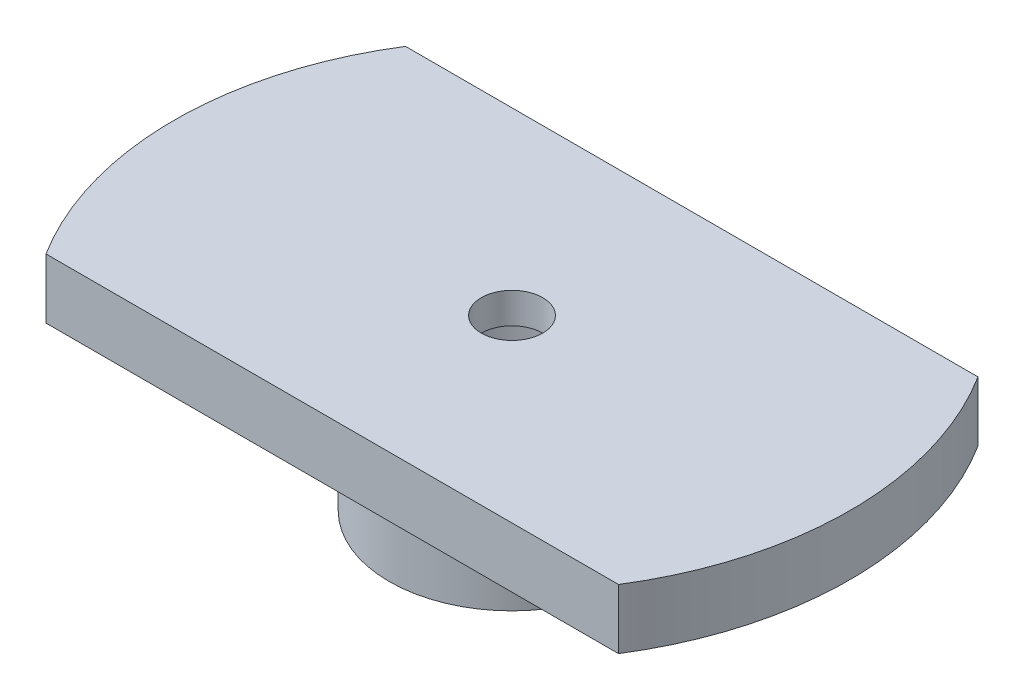
SolidWorks part; units mm, degrees
ref_plane "Front Plane" through (0, 0, 0) normal (0, 0, 1) x (1, 0, 0)
ref_plane "Top Plane" through (0, 0, 0) normal (0, 1, 0) x (1, 0, 0)
ref_plane "Right Plane" through (0, 0, 0) normal (1, 0, 0) x (0, 0, -1)
sketch "Sketch1" plane through (0, 0, 0) normal (0, 1, 0) x (1, 0, 0)
  line L0 (17, 5.85) -> (-17, 5.85)
  line L1 (0, 5.85) -> (0, -5.85) construction
  line L2 (-22.85, 0) -> (22.85, 0) construction
  line L3 (17, -5.85) -> (-17, -5.85)
  arc A0 (-17, 5.85) -> (-22.85, 0) centre (-17, 0) ccw
  arc A1 (-17, -5.85) -> (-22.85, 0) centre (-17, 0) cw
  arc A2 (17, -5.85) -> (22.85, 0) centre (17, 0) ccw
  arc A3 (17, 5.85) -> (22.85, 0) centre (17, 0) cw
  point P4 (0, 0)
  dimension "D1" = 45.7
  dimension "D2" = 11.7
extrude "Boss-Extrude1" add sketch "Sketch1" against normal blind 1.95
sketch "Sketch2" plane through (0, -1.95, 0) normal (0, -1, 0) x (1, 0, 0)
  circle A0 centre (0, 0) radius 4
  dimension "D1" = 8
extrude "Boss-Extrude2" add sketch "Sketch2" along normal blind 3.55
sketch "Sketch3" plane through (0, -5.5, 0) normal (0, -1, 0) x (1, 0, 0)
  circle A0 centre (0, 0) radius 2.86
  dimension "D1" = 5.72
extrude "Cut-Extrude1" cut sketch "Sketch3" against normal blind 4.5
sketch "Sketch4" plane through (0, -1, 0) normal (0, -1, 0) x (1, 0, 0)
  circle A0 centre (0, 0) radius 1
  dimension "D1" = 2
extrude "Cut-Extrude2" cut sketch "Sketch4" against normal up to surface (1 mm away) up to face at (0, 0, 0)
sketch "Sketch5" plane through (0, 0, 0) normal (0, 1, 0) x (1, 0, 0)
  circle A0 centre (0, 0) radius 11
  dimension "D1" = 22
extrude "Cut-Extrude3" cut sketch "Sketch5" against normal through all both and the other way through all flip side to cut
